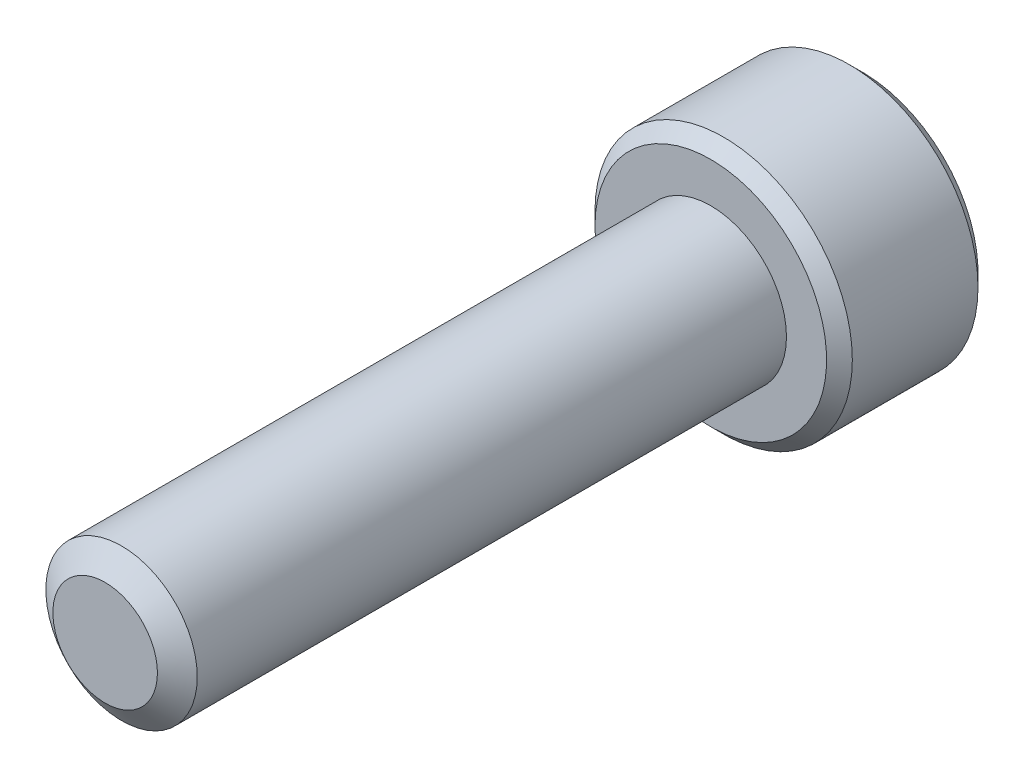
SolidWorks part; units mm, degrees
other "DetailItem1"
material "1.4310 (X10CrNi18-8)"
ref_plane "Front Plane" through (0, 0, 0) normal (0, 0, 1) x (1, 0, 0)
ref_plane "Top Plane" through (0, 0, 0) normal (0, 1, 0) x (1, 0, 0)
ref_plane "Right Plane" through (0, 0, 0) normal (1, 0, 0) x (0, 0, -1)
sketch "Sketch1" plane through (0, 0, 0) normal (0, 0, 1) x (1, 0, 0)
  circle A0 centre (0, 0) radius 2.5
  dimension "OD" = 5
extrude "Extrude1" add sketch "Sketch1" against normal blind 20
sketch "Sketch2" plane through (0, 0, 0) normal (0, 0, 1) x (1, 0, 0)
  circle A0 centre (0, 0) radius 2.5 construction
  circle A1 centre (0, 0) radius 2.5
curve "Helix/Spiral1" pitch 0.8 height 20.8 turns 26 parameters "pitch"=0.8
sketch "Sketch3" plane through (0, 0, 0) normal (1, 0, 0) x (0, 0, -1)
  line L0 (-0.7, 2.5) -> (-0.4, 1.9804)
  line L1 (-0.4, 1.9804) -> (-0.3, 1.9804)
  line L2 (-0.3, 1.9804) -> (0, 2.5)
  line L3 (-0.7, 2.5) -> (0, 2.5)
  line L4 (-0.35, 2.5) -> (-0.35, 1.9804) construction
  line L5 (-0.55, 2.2402) -> (-0.15, 2.2402) construction
  line L6 (0, 2.5) -> (0, -2.5) construction
  dimension "D1" = 0.1
  dimension "D2" = 0.4
  dimension "D3" = 60
sweep "Cut-Sweep1" [suppressed] cut profiles "Sketch3" path "Helix/Spiral1"
sketch "Sketch4" plane through (0, 0, 0) normal (1, 0, 0) x (0, 0, -1)
  line L0 (0.5417, 2.5) -> (0, 1.7264)
  line L1 (0, 1.7264) -> (0, 2.5)
  line L2 (0.5417, 2.5) -> (0, 2.5)
  line L3 (-0.7, 2.5) -> (0, 2.5) construction
  line L4 (0, 0) -> (7.0209, 0) construction
  dimension "D1" = 55
  dimension "D2" = 0.254
revolve "Cut-Revolve1" cut sketch "Sketch4" angle 360 about L4
sketch "Sketch6" plane through (0, 0, -20) normal (0, 0, -1) x (-1, 0, 0)
  circle A0 centre (0, 0) radius 4.25
  dimension "head dia" = 8.5
extrude "Extrude2" add sketch "Sketch6" along normal blind 5
sketch "Sketch7" plane through (0, 0, -25) normal (0, 0, -1) x (-1, 0, 0)
  line L1 (0, 2.3094) -> (-2, 1.1547)
  line L2 (-2, 1.1547) -> (-2, -1.1547)
  line L3 (-2, -1.1547) -> (0, -2.3094)
  line L4 (0, -2.3094) -> (2, -1.1547)
  line L5 (2, -1.1547) -> (2, 1.1547)
  line L6 (2, 1.1547) -> (0, 2.3094)
  circle A0 centre (0, 0) radius 2 construction
  dimension "hex dia" = 4
extrude "Cut-Extrude1" cut sketch "Sketch7" against normal blind 3
sketch "Sketch8" plane through (0, 0, -25) normal (0, 0, -1) x (-1, 0, 0)
  circle A0 centre (0, 0) radius 2.3094
extrude "Cut-Extrude2" cut sketch "Sketch8" against normal through all draft 45
chamfer "Chamfer1" distance 0.425 angle 45 2 edges at (-4.25, 0, -25) (-4.25, 0, -20)
sketch "Sketch10" plane through (0, 0, -20) normal (0, 0, 1) x (1, 0, 0)
  circle A1 centre (0, 0) radius 2.5
  circle A2 centre (0, 0) radius 2.5
  dimension "D1" = 0
ref_plane "Plane1" through (0, 0, 0) normal (0, 0, 1) x (1, 0, 0)
extrude "partial thread" [suppressed] add sketch "Sketch10" along normal up to surface (13 mm away) separate body up to plane "Plane1"
chamfer "Chamfer2" [suppressed] distance 0.1 angle 45
combine bodies "Combine1" [suppressed] operation type add bodies to combine 107 108
sketch "Sketch9" plane through (0, 0, 0) normal (1, 0, 0) x (0, 0, -1)
  line L0 (0, 2.5) -> (0, -2.5) construction
  line L1 (2, 2.5) -> (2, -2.5) construction
  dimension "D1" = 2
equation "\"D3@Helix/Spiral1\" = \"screw length@Extrude1\"+\"pitch@Helix/Spiral1\""
equation "\"D1@Sketch3\" = \"pitch@Helix/Spiral1\"*.125"
equation "\"D2@Sketch3\" = \"pitch@Helix/Spiral1\"*.5"
equation "\"D1@Cut-Extrude1\" = \"hex dia@Sketch7\"*.75"
equation "\"D1@Chamfer1\" = \"head dia@Sketch6\"*.05"
equation "\"D1@Sketch9\" = \"pitch@Helix/Spiral1\"*2.5"
equation "\"D1@Chamfer2\"=\"OD@Sketch1\"*.02"
